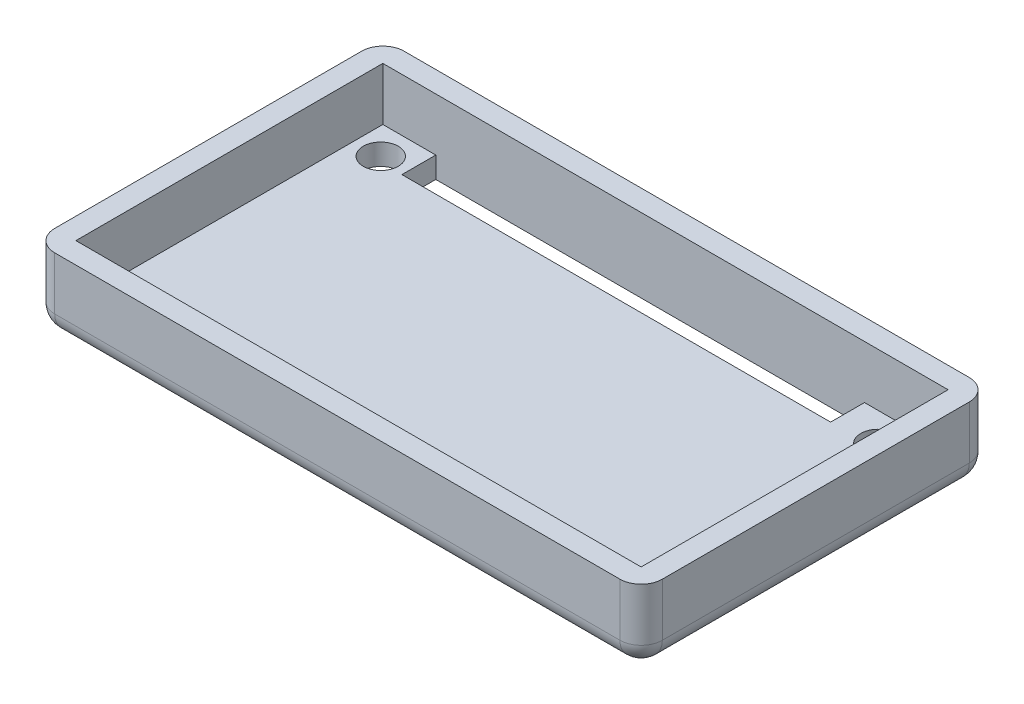
SolidWorks part; units mm, degrees
ref_plane "Front Plane" through (0, 0, 0) normal (0, 0, 1) x (1, 0, 0)
ref_plane "Top Plane" through (0, 0, 0) normal (0, 1, 0) x (1, 0, 0)
ref_plane "Right Plane" through (0, 0, 0) normal (1, 0, 0) x (0, 0, -1)
sketch "Sketch1" plane through (0, 0, 0) normal (0, 1, 0) x (1, 0, 0)
  line L1 (0, 0) -> (57.4, 0)
  line L2 (0, 0) -> (0, 33)
  line L3 (0, 33) -> (57.4, 33)
  line L4 (57.4, 0) -> (57.4, 33)
  dimension "D1" = 57.4
  dimension "D2" = 33
extrude "Boss-Extrude1" add sketch "Sketch1" along normal blind 7
fillet "Fillet1" radius 2 8 edges at (28.7, 0, 0) (57.4, 0, -16.5) (28.7, 0, -33) (0, 0, -16.5) (57.4, 3.5, -33) (0, 3.5, -33) (57.4, 3.5, 0) (0, 3.5, 0)
shell "Shell3" thickness 2 removed face at (28.7, 7, -16.5)
sketch "Sketch2" plane through (0, 2, 0) normal (0, 1, 0) x (1, 0, 0)
  line L0 (4.5, 28.3) -> (4.5, 4.7) construction
  line L1 (2, 2) -> (2, 31) construction
  line L2 (2, 31) -> (2, 2) construction
  circle A0 centre (4.5, 28.3) radius 1.65
  circle A1 centre (51.5, 28.3) radius 1.65
  circle A2 centre (4.5, 4.7) radius 1.65
  circle A3 centre (51.5, 4.7) radius 1.65
  point P10 (2, 16.5)
  point P11 (4.5, 16.5)
  point P14 (51.5, 5.8122)
  point P15 (0, 0)
  dimension "D1" = 3.3
  dimension "D2" = 47
  dimension "D3" = 23.6
  dimension "D4" = 2.5
extrude "Cut-Extrude1" cut sketch "Sketch2" against normal through all
sketch "Sketch3" plane through (0, 2, 0) normal (0, 1, 0) x (1, 0, 0)
  line L0 (55.4, 31) -> (2, 31) construction
  line L1 (7, 31) -> (47.5, 31)
  line L2 (7, 31) -> (7, 27.8)
  line L3 (7, 27.8) -> (47.5, 27.8)
  line L4 (47.5, 31) -> (47.5, 27.8)
  line L5 (2, 31) -> (2, 2) construction
  line L6 (2, 16.5) -> (55.4, 16.5) construction
  line L7 (55.4, 2) -> (55.4, 31) construction
  line L8 (47.5, 2) -> (47.5, 5.2)
  line L9 (7, 5.2) -> (47.5, 5.2)
  line L10 (7, 2) -> (7, 5.2)
  line L11 (7, 2) -> (47.5, 2)
  circle A0 centre (51.5, 28.3) radius 1.65 construction
  dimension "D1" = 5
  dimension "D2" = 4
  dimension "D3" = 3.2
extrude "Cut-Extrude2" cut sketch "Sketch3" against normal through all
